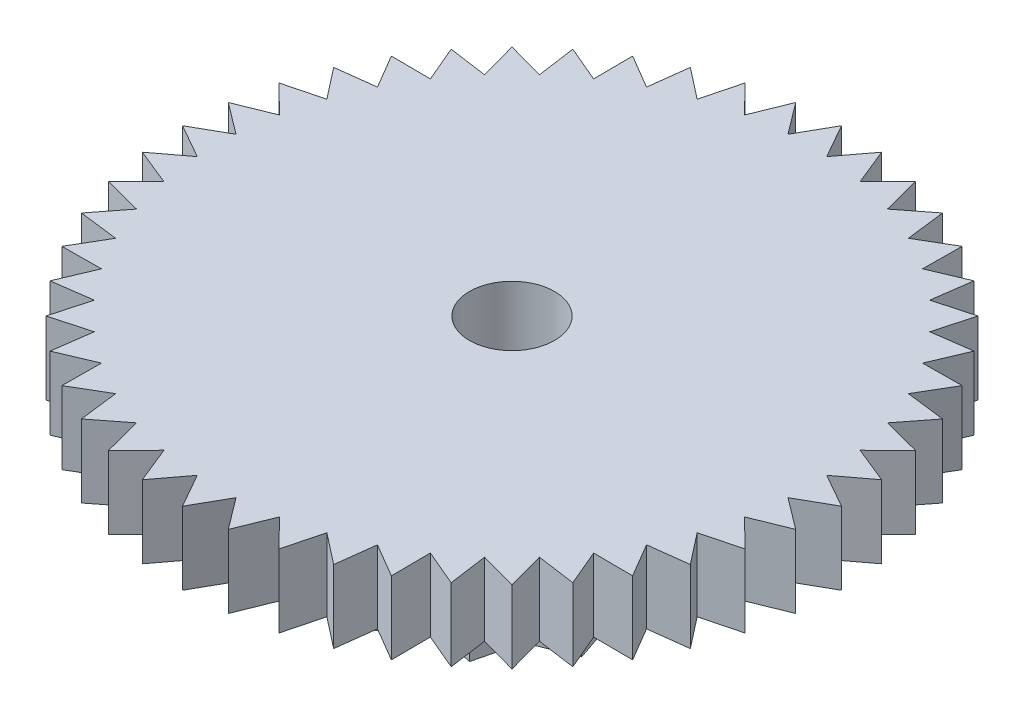
SolidWorks part; units mm, degrees
ref_plane "Front Plane" through (0, 0, 0) normal (0, 0, 1) x (1, 0, 0)
ref_plane "Top Plane" through (0, 0, 0) normal (0, 1, 0) x (1, 0, 0)
ref_plane "Right Plane" through (0, 0, 0) normal (1, 0, 0) x (0, 0, -1)
sketch "Sketch1" plane through (0, 0, 0) normal (0, 0, 1) x (1, 0, 0)
  line L0 (-6.2, 3.8) -> (-6.2, 2.43)
  line L1 (-6.2, 2.43) -> (-2.65, 2.43)
  line L2 (-2.65, 2.43) -> (-2.65, 0)
  line L3 (-2.65, 0) -> (0, 0)
  line L4 (-6.2, 3.8) -> (0, 3.8)
  line L5 (0, 3.8) -> (0, 0) construction
  line L6 (0, 0) -> (0, 3.8)
  dimension "D1" = 6.2
  dimension "D2" = 1.37
  dimension "D3" = 3.8
  dimension "D4" = 2.65
revolve "Revolve1" add sketch "Sketch1" angle 360 about L5
sketch "Sketch2" plane through (0, 3.8, 0) normal (0, 1, 0) x (1, 0, 0)
  circle A0 centre (0, 0) radius 0.8
  dimension "D1" = 1.6
extrude "Cut-Extrude1" cut sketch "Sketch2" against normal through all
sketch "Sketch3" plane through (0, 3.8, 0) normal (0, 1, 0) x (1, 0, 0)
  line L0 (0, 0) -> (0, 6.2) construction
  line L2 (0, 0) -> (0.4055, 6.1867) construction
  line L3 (0, 0) -> (0.8093, 6.147) construction
  line L4 (0, 6.2) -> (0.3642, 5.5572)
  line L5 (0.3642, 5.5572) -> (0.8093, 6.147)
  circle A0 centre (0, 0) radius 6.2 construction
  circle A1 centre (0, 0) radius 5.5692 construction
  arc A2 (0, 6.2) -> (0.8093, 6.147) centre (0, 0) cw
  dimension "D1" = 7.5
extrude "Cut-Extrude2" cut sketch "Sketch3" against normal through all
ref_axis "Axis1" through (0, 0, 0) along (0, 1, 0)
pattern_circular "CirPattern1" count 48 over 360 about axis through (0, 0, 0) along (0, 1, 0) of "Cut-Extrude2"
sketch "Sketch4" plane through (0, 0, 0) normal (0, -1, 0) x (1, 0, 0)
  line L0 (0, 0) -> (0, 2.65) construction
  line L1 (0, 0) -> (1.4327, 2.2293) construction
  line L2 (0.7466, 2.5427) -> (0, 0) construction
  line L3 (0, 2.65) -> (0.6094, 2.0756)
  line L4 (0.6094, 2.0756) -> (1.4327, 2.2293)
  circle A0 centre (0, 0) radius 2.65 construction
  circle A1 centre (0, 0) radius 2.65 construction
  arc A2 (0, 2.65) -> (1.4327, 2.2293) centre (0, 0) cw
  circle A3 centre (0, 0) radius 2.1632 construction
  dimension "D1" = 32.727
extrude "Cut-Extrude3" cut sketch "Sketch4" against normal up to surface (2.43 mm away) up to face at (0, 2.43, 0)
pattern_circular "CirPattern2" count 11 over 360 about axis through (0, 0, 0) along (0, 1, 0) of "Cut-Extrude3"
